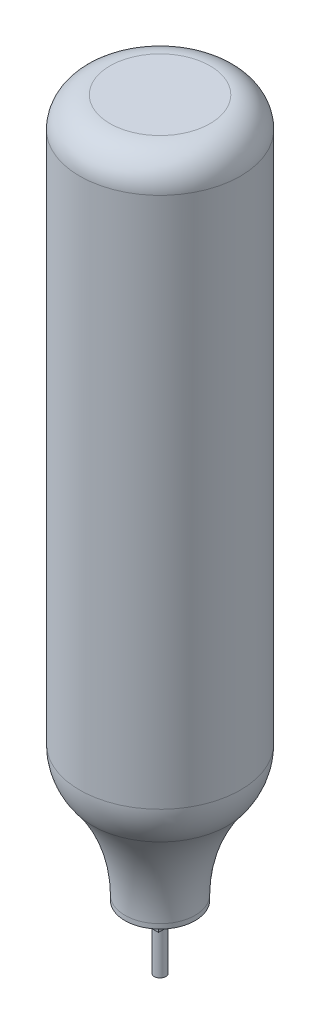
SolidWorks part; units mm, degrees
ref_plane "Front Plane" through (0, 0, 0) normal (0, 0, 1) x (1, 0, 0)
ref_plane "Top Plane" through (0, 0, 0) normal (0, 1, 0) x (1, 0, 0)
ref_plane "Right Plane" through (0, 0, 0) normal (1, 0, 0) x (0, 0, -1)
sketch "Sketch1" plane through (0, 0, 0) normal (0, 1, 0) x (1, 0, 0)
  circle A0 centre (0, 0) radius 26.5
  dimension "D1" = 53
extrude "Boss-Extrude1" add sketch "Sketch1" along normal blind 230
sketch "Sketch2" plane through (0, 0, 0) normal (0, -1, 0) x (1, 0, 0)
  circle A0 centre (0, 0) radius 11.5644
  circle A1 centre (0, 0) radius 26.5 construction
  circle A2 centre (0, 0) radius 26.5
  circle M3 centre (0, 0) radius 26.5
extrude "Cut-Extrude1" cut sketch "Sketch2" against normal blind 25.4 contours A0 M3 region at (-25.7505, 0, 0)
fillet "Fillet1" radius 20 1 edges at (0, 25.4, -26.5)
fillet "Fillet2" radius 50 1 edges at (0, 25.4, -11.5644)
fillet "Fillet3" radius 10 1 edges at (0, 230, 26.5)
sketch "Sketch3" plane through (0, 0, 0) normal (0, -1, 0) x (1, 0, 0)
  line L1 (3.4738, -3.9949) -> (-3.4738, -3.9949)
  line L2 (3.4738, -3.9949) -> (3.4738, 3.9949)
  line L3 (3.4738, 3.9949) -> (-3.4738, 3.9949)
  line L4 (-3.4738, -3.9949) -> (-3.4738, 3.9949)
  line L5 (3.4738, -3.9949) -> (-3.4738, 3.9949) construction
  line L6 (3.4738, 3.9949) -> (-3.4738, -3.9949) construction
  point P0 (0, 0)
extrude "Boss-Extrude2" add sketch "Sketch3" along normal blind 5.4
sketch "Sketch4" plane through (0, -5.4, 0) normal (0, -1, 0) x (-1, 0, 0)
  circle A0 centre (0, 0) radius 1.895
extrude "Boss-Extrude3" add sketch "Sketch4" along normal blind 15.4
